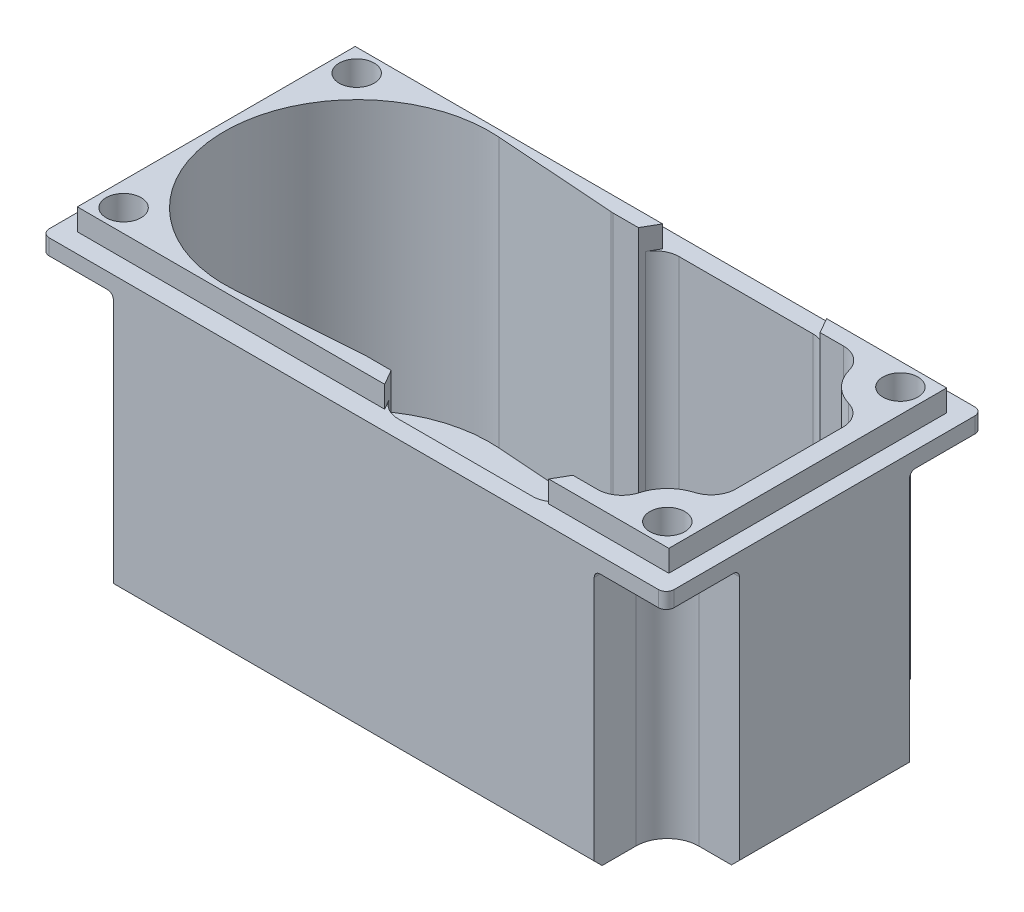
SolidWorks part; units mm, degrees
ref_plane "Front Plane" through (0, 0, 0) normal (0, 0, 1) x (1, 0, 0)
ref_plane "Top Plane" through (0, 0, 0) normal (0, 1, 0) x (1, 0, 0)
ref_plane "Right Plane" through (0, 0, 0) normal (1, 0, 0) x (0, 0, -1)
sketch "Sketch1" plane through (0, 0, 0) normal (0, 1, 0) x (1, 0, 0)
  line L1 (-20.193, 10.2235) -> (20.193, 10.2235)
  line L2 (-20.193, 10.2235) -> (-20.193, -10.2235)
  line L3 (-20.193, -10.2235) -> (20.193, -10.2235)
  line L4 (20.193, 10.2235) -> (20.193, -10.2235)
  line L5 (-20.193, 10.2235) -> (20.193, -10.2235) construction
  line L6 (-20.193, -10.2235) -> (20.193, 10.2235) construction
  point P0 (0, 0)
  dimension "D1" = 40.386
  dimension "D2" = 20.447
extrude "Boss-Extrude1" add sketch "Sketch1" along normal blind 17.78
fillet "Fillet1" radius 0.508 4 edges at (20.193, 8.89, 10.2235) (20.193, 8.89, -10.2235) (-20.193, 8.89, -10.2235) (-20.193, 8.89, 10.2235)
chamfer "Chamfer1" distance 0.508 angle 45 8 edges at (0, 0, -10.2235) (-20.0442, 0, -10.0747) (20.0442, 0, -10.0747) (-20.193, 0, 0) (20.193, 0, 0) (-20.0442, 0, 10.0747) (20.0442, 0, 10.0747) (0, 0, 10.2235)
hole_wizard "#2 Clearance Hole1" positions "Sketch4" profile "Sketch5" hole size "#2" standard "ANSI Inch" end condition up to next
sketch "Sketch4" plane through (0, 17.78, 0) normal (0, 1, 0) x (1, 0, 0)
  line L1 (-17.5704, 7.5311) -> (17.5704, 7.5311)
  line L2 (-17.5704, 7.5311) -> (-17.5704, -7.5311)
  line L3 (-17.5704, -7.5311) -> (17.5704, -7.5311)
  line L4 (17.5704, 7.5311) -> (17.5704, -7.5311)
  line L5 (-17.5704, 7.5311) -> (17.5704, -7.5311) construction
  line L6 (-17.5704, -7.5311) -> (17.5704, 7.5311) construction
  point P2 (17.5704, -7.5311)
  point P81 (-17.5704, 7.5311)
  point P82 (-17.5704, -7.5311)
  point P83 (17.5704, 7.5311)
  point P97 (0, 0)
  dimension "D1" = 15.0622
  dimension "D2" = 35.1409
sketch "Sketch5" plane through (17.5704, 17.78, 7.5311) normal (1, 0, 0) x (0, 0, 1)
  line L0 (0, 0) -> (0, 17.78)
  line L1 (0, 17.78) -> (1.1303, 17.78)
  line L2 (1.1303, 17.78) -> (1.1303, 0)
  line L5 (1.1303, 0) -> (0, 0)
  line L11 (0, -6.35) -> (0, 107.95) construction
  dimension "Thru Hole Dia." = 2.2606
  dimension "Thru Hole Depth" = 17.78
sketch "Sketch6" plane through (0, 17.78, 0) normal (0, 1, 0) x (1, 0, 0)
  circle A0 centre (-10.0147, 0) radius 8.5725
  circle A2 centre (-17.5704, 7.5311) radius 1.1303 construction
  dimension "D1" = 17.145
  dimension "D2" = 10.668
extrude "Cut-Extrude1" cut sketch "Sketch6" against normal offset from surface (16.002 mm away) 1.778 up to face at (17.5704, 0, 8.6614)
sketch "Sketch10" plane through (0, 17.78, 0) normal (0, 1, 0) x (1, 0, 0)
  line L3 (-1.4531, -7.9883) -> (14.9881, -7.9883)
  line L5 (17.9581, -4.9374) -> (17.9581, 4.8667)
  line L7 (14.9172, 7.9883) -> (-1.524, 7.9883)
  line L10 (20.193, -9.7155) -> (20.193, 9.7155) construction
  line L11 (19.685, 10.2235) -> (-19.685, 10.2235) construction
  line L12 (6.6966, 7.9883) -> (6.6966, 10.2235) construction
  line L13 (-1.524, 7.9883) -> (-9.4045, 8.5507)
  line L14 (17.9581, -0.0353) -> (20.193, 0) construction
  line L16 (-9.4099, -8.5511) -> (-1.4531, -7.9883)
  line L17 (-10.0147, 0) -> (17.9581, -0.0353) construction
  line L18 (6.7675, -7.9883) -> (6.7675, -10.2235) construction
  line L19 (-19.685, -10.2235) -> (19.685, -10.2235) construction
  arc A2 (14.9172, 7.9883) -> (17.9581, 4.8667) centre (17.5704, 7.5311) ccw
  arc A3 (17.9581, -4.9374) -> (14.9881, -7.9883) centre (17.5704, -7.5311) ccw
  circle A4 centre (17.5704, -7.5311) radius 1.1303 construction
  circle A5 centre (-10.0147, 0) radius 8.5725 construction
  circle A6 centre (-10.0147, 0) radius 8.5725 construction
  arc A7 (-9.4099, -8.5511) -> (-9.4045, 8.5507) centre (-10.0147, 0) ccw
  circle M17 centre (-10.0147, 0) radius 8.5725
  dimension "D3" = 15.9766
  dimension "D1" = 1.524
extrude "Cut-Extrude4" cut sketch "Sketch10" against normal up to surface (16.002 mm away) contours A3 L5 A2 L7 L3 M17 region at (6.8897, 17.78, 0.007) up to face at (-10.0147, 1.778, 8.5725)
fillet "Fillet3" radius 1.5875 6 edges at (14.9881, 9.779, 7.9883) (17.9581, 9.779, 4.9374) (17.9581, 9.779, -4.8667) (14.9172, 9.779, -7.9883) (-1.4531, 9.779, 7.9883) (-1.524, 9.779, -7.9883)
sketch "Sketch9" plane through (0, 0, 0) normal (0, -1, 0) x (1, 0, 0)
  line L0 (-17.5704, -5.4991) -> (-20.193, -5.4991)
  line L1 (-15.5384, 7.5311) -> (-15.5384, 10.2235)
  line L2 (-15.5384, -7.5311) -> (-15.5384, -10.2235)
  line L4 (19.685, 10.2235) -> (-19.685, 10.2235)
  line L5 (20.193, -9.7155) -> (20.193, 9.7155)
  line L6 (-19.685, -10.2235) -> (19.685, -10.2235)
  line L7 (-20.193, 9.7155) -> (-20.193, -9.7155)
  line L8 (19.685, 10.2235) -> (15.5384, 10.2235)
  line L9 (20.193, -9.7155) -> (20.193, -5.4991)
  line L10 (-19.685, -10.2235) -> (-15.5384, -10.2235)
  line L11 (-20.193, 9.7155) -> (-20.193, 5.4991)
  line L12 (-17.5704, 5.4991) -> (-20.193, 5.4991)
  line L13 (-20.193, 5.4991) -> (-17.5704, 5.4991)
  line L14 (17.5704, 5.4991) -> (20.193, 5.4991)
  line L16 (15.5384, 7.5311) -> (15.5384, 10.2235)
  line L17 (15.5384, 10.2235) -> (15.5384, 7.5311)
  line L18 (15.5384, -7.5311) -> (15.5384, -10.2235)
  line L19 (20.193, 5.4991) -> (20.193, 9.7155)
  line L20 (17.5704, -5.4991) -> (20.193, -5.4991)
  line L21 (15.5384, -10.2235) -> (19.685, -10.2235)
  line L22 (-20.193, -5.4991) -> (-20.193, -9.7155)
  line L24 (-15.5384, 10.2235) -> (-19.685, 10.2235)
  arc A0 (-15.5384, -7.5311) -> (-17.5704, -5.4991) centre (-17.5704, -7.5311) ccw
  arc A1 (-17.5704, 5.4991) -> (-15.5384, 7.5311) centre (-17.5704, 7.5311) ccw
  arc A2 (15.5384, 7.5311) -> (17.5704, 5.4991) centre (17.5704, 7.5311) ccw
  arc A3 (17.5704, -5.4991) -> (15.5384, -7.5311) centre (17.5704, -7.5311) ccw
  arc A8 (20.193, 9.7155) -> (19.685, 10.2235) centre (19.685, 9.7155) ccw
  arc A9 (19.685, -10.2235) -> (20.193, -9.7155) centre (19.685, -9.7155) ccw
  arc A10 (-20.193, -9.7155) -> (-19.685, -10.2235) centre (-19.685, -9.7155) ccw
  arc A11 (-19.685, 10.2235) -> (-20.193, 9.7155) centre (-19.685, 9.7155) ccw
  arc A12 (20.193, 9.7155) -> (19.685, 10.2235) centre (19.685, 9.7155) ccw
  arc A13 (19.685, -10.2235) -> (20.193, -9.7155) centre (19.685, -9.7155) ccw
  arc A14 (-20.193, -9.7155) -> (-19.685, -10.2235) centre (-19.685, -9.7155) ccw
  arc A15 (-19.685, 10.2235) -> (-20.193, 9.7155) centre (-19.685, 9.7155) ccw
  circle M13 centre (17.5704, 7.5311) radius 1.1303
  circle M14 centre (-17.5704, -7.5311) radius 1.1303
  circle M15 centre (-17.5704, 7.5311) radius 1.1303
  circle M16 centre (17.5704, -7.5311) radius 1.1303
  line M17 (-19.685, 9.7155) -> (-19.685, -9.7155)
  line M18 (-19.685, -9.7155) -> (19.685, -9.7155)
  line M19 (19.685, -9.7155) -> (19.685, 9.7155)
  line M20 (19.685, 9.7155) -> (-19.685, 9.7155)
  dimension "D1" = 4.064
  dimension "D2" = 0
extrude "Cut-Extrude5" cut sketch "Sketch9" against normal offset from surface (16.764 mm away) 1.016 contours L12 A1 L1 M20 M17 M15 | L24 A15 L11 L12 L1 M17 M20 | L2 A0 L0 M17 M18 M14 | L22 A14 L10 L2 L0 M18 M17 | L16 A2 L14 M19 M20 M13 | L19 A12 L8 L16 L14 M20 M19 | L20 A3 L18 M18 M19 M16 | L21 A13 L9 L20 L18 M19 M18 region at (-16.1754, 0, -6.1361) region at (-19.7513, 0, -7.6073) region at (-19.6259, 0, 7.6073) region at (-19.939, 0, 5.5654) region at (17.6117, 0, -9.7818) region at (15.5976, 0, -8.6233) region at (17.6117, 0, 9.6564) region at (15.6048, 0, 9.9695) up to face at (6.6431, 17.78, 0.0111)
fillet "Fillet5" radius 0.381 12 edges at (-15.5384, 16.764, -8.8773) (-18.8817, 16.764, -5.4991) (18.8817, 16.764, -5.4991) (15.5384, 16.764, -8.8773) (15.5384, 16.764, 8.8773) (18.8817, 16.764, 5.4991) (-18.8817, 16.764, 5.4991) (-15.5384, 16.764, 8.8773) (-16.1336, 16.764, -6.0943) (16.1336, 16.764, -6.0943) (16.1336, 16.764, 6.0943) (-16.1336, 16.764, 6.0943)
sketch "Sketch11" plane through (0, 0, 0) normal (0, -1, 0) x (1, 0, 0)
  line L0 (-1.397, 7.9883) -> (13.515, 7.9883) construction
  line L1 (11.3311, -9.144) -> (16.6104, 0) construction
  line L2 (16.6104, 0) -> (11.3311, 9.144) construction
  line L3 (11.3311, 9.144) -> (0.7725, 9.144) construction
  line L4 (0.7725, 9.144) -> (-4.5068, 0) construction
  line L5 (-4.5068, 0) -> (0.7725, -9.144) construction
  line L6 (0.7725, -9.144) -> (11.3311, -9.144) construction
  line L8 (17.9581, -3.4228) -> (17.9581, 3.4957) construction
  circle A0 centre (6.0518, 0) radius 7.62
  circle A1 centre (6.0518, 0) radius 9.144 construction
  dimension "D1" = 15.24
  dimension "D2" = 11.9062
  dimension "D3" = 18.288
extrude "Cut-Extrude7" cut sketch "Sketch11" against normal through all contours A0
sketch "Sketch12" plane through (0, 17.78, 0) normal (0, 1, 0) x (1, 0, 0)
  line L5 (-1.5804, 7.9923) -> (-9.4045, 8.5507) construction
  line L6 (-19.1135, 8.9789) -> (19.1135, 8.9789)
  line L14 (-19.1135, 8.9789) -> (-19.1135, -8.9789)
  line L15 (-19.1135, -8.9789) -> (19.1135, -8.9789)
  line L16 (19.1135, 8.9789) -> (19.1135, -8.9789)
  line L17 (-19.1135, 8.9789) -> (19.1135, -8.9789) construction
  line L18 (-19.1135, -8.9789) -> (19.1135, 8.9789) construction
  line L19 (-9.4099, -8.5511) -> (-1.509, -7.9923) construction
  line L20 (-1.397, -7.9883) -> (13.515, -7.9883) construction
  line L21 (13.4425, 7.9883) -> (-1.4674, 7.9883) construction
  line L22 (17.9581, -3.4957) -> (17.9581, 3.4228) construction
  line L23 (17.9581, -3.4957) -> (17.9581, 3.4228)
  line L24 (13.4425, 7.9883) -> (-1.4674, 7.9883)
  line L25 (-1.397, -7.9883) -> (13.515, -7.9883)
  line L26 (-9.4099, -8.5511) -> (-1.509, -7.9923)
  line L27 (-1.5804, 7.9923) -> (-9.4045, 8.5507)
  circle A16 centre (17.5704, -7.5311) radius 1.1303 construction
  circle A17 centre (17.5704, 7.5311) radius 1.1303 construction
  circle A18 centre (-17.5704, -7.5311) radius 1.1303 construction
  circle A19 centre (-17.5704, 7.5311) radius 1.1303 construction
  circle A20 centre (17.5704, -7.5311) radius 1.1303
  circle A21 centre (17.5704, 7.5311) radius 1.1303
  circle A22 centre (-17.5704, -7.5311) radius 1.1303
  circle A23 centre (-17.5704, 7.5311) radius 1.1303
  arc A24 (-9.4045, 8.5507) -> (-9.4099, -8.5511) centre (-10.0147, 0) ccw construction
  arc A25 (-1.5804, 7.9923) -> (-1.4674, 7.9883) centre (-1.4674, 9.5758) ccw construction
  arc A26 (-1.397, -7.9883) -> (-1.509, -7.9923) centre (-1.397, -9.5758) ccw construction
  arc A27 (14.9736, 6.8201) -> (13.4425, 7.9883) centre (13.4425, 6.4008) ccw construction
  arc A28 (14.9736, 6.8201) -> (16.8156, 4.9467) centre (17.5704, 7.5311) ccw construction
  arc A29 (17.9581, 3.4228) -> (16.8156, 4.9467) centre (16.3706, 3.4228) ccw construction
  arc A30 (16.823, -5.0173) -> (17.9581, -3.4957) centre (16.3706, -3.4957) ccw construction
  arc A31 (16.823, -5.0173) -> (15.0442, -6.827) centre (17.5704, -7.5311) ccw construction
  arc A32 (13.515, -7.9883) -> (15.0442, -6.827) centre (13.515, -6.4008) ccw construction
  arc A33 (13.515, -7.9883) -> (15.0442, -6.827) centre (13.515, -6.4008) ccw
  arc A34 (16.823, -5.0173) -> (15.0442, -6.827) centre (17.5704, -7.5311) ccw
  arc A35 (16.823, -5.0173) -> (17.9581, -3.4957) centre (16.3706, -3.4957) ccw
  arc A36 (17.9581, 3.4228) -> (16.8156, 4.9467) centre (16.3706, 3.4228) ccw
  arc A37 (14.9736, 6.8201) -> (16.8156, 4.9467) centre (17.5704, 7.5311) ccw
  arc A38 (14.9736, 6.8201) -> (13.4425, 7.9883) centre (13.4425, 6.4008) ccw
  arc A39 (-1.5804, 7.9923) -> (-1.4674, 7.9883) centre (-1.4674, 9.5758) ccw
  arc A40 (-1.397, -7.9883) -> (-1.509, -7.9923) centre (-1.397, -9.5758) ccw
  arc A41 (-9.4045, 8.5507) -> (-9.4099, -8.5511) centre (-10.0147, 0) ccw
  point P0 (0, 0)
  dimension "D1" = 17.9578
  dimension "D2" = 38.227
extrude "Boss-Extrude3" add sketch "Sketch12" along normal blind 1.397
sketch "Sketch13" plane through (0, 1.778, 0) normal (0, 1, 0) x (1, 0, 0)
  line L1 (11.2945, -9.0805) -> (16.5371, 0)
  line L2 (16.5371, 0) -> (11.2945, 9.0805)
  line L3 (11.2945, 9.0805) -> (0.8092, 9.0805)
  line L4 (0.8092, 9.0805) -> (-4.4334, 0)
  line L5 (-4.4334, 0) -> (0.8092, -9.0805)
  line L6 (0.8092, -9.0805) -> (11.2945, -9.0805)
  circle A0 centre (6.0518, 0) radius 9.0805 construction
  dimension "D1" = 18.161
extrude "Cut-Extrude8" cut sketch "Sketch13" along normal through all
fillet "Fillet7" radius 1.5875 4 edges at (0.8092, 9.779, -9.0805) (11.2945, 9.779, -9.0805) (11.2945, 9.779, 9.0805) (0.8092, 9.779, 9.0805)
sketch "Sketch14" plane through (0, 19.177, 0) normal (0, 1, 0) x (1, 0, 0)
  line L0 (1.7257, 9.0805) -> (10.3779, 9.0805) construction
  line L1 (11.2945, 9.0805) -> (0.8092, 9.0805)
  line L2 (0.8092, 9.0805) -> (-4.4334, 0)
  line L3 (-4.4334, 0) -> (0.8092, -9.0805)
  line L4 (0.8092, -9.0805) -> (11.2945, -9.0805)
  line L5 (11.2945, -9.0805) -> (16.5371, 0)
  line L6 (16.5371, 0) -> (11.2945, 9.0805)
  circle A0 centre (6.0518, 0) radius 9.0805 construction
extrude "Cut-Extrude9" cut sketch "Sketch14" against normal up to surface (1.397 mm away) up to face at (0, 17.78, 0)
equation "\"D1@Boss-Extrude1\"=.7"
equation "\"D3@Sketch10\"=0.709in-2*.04"
